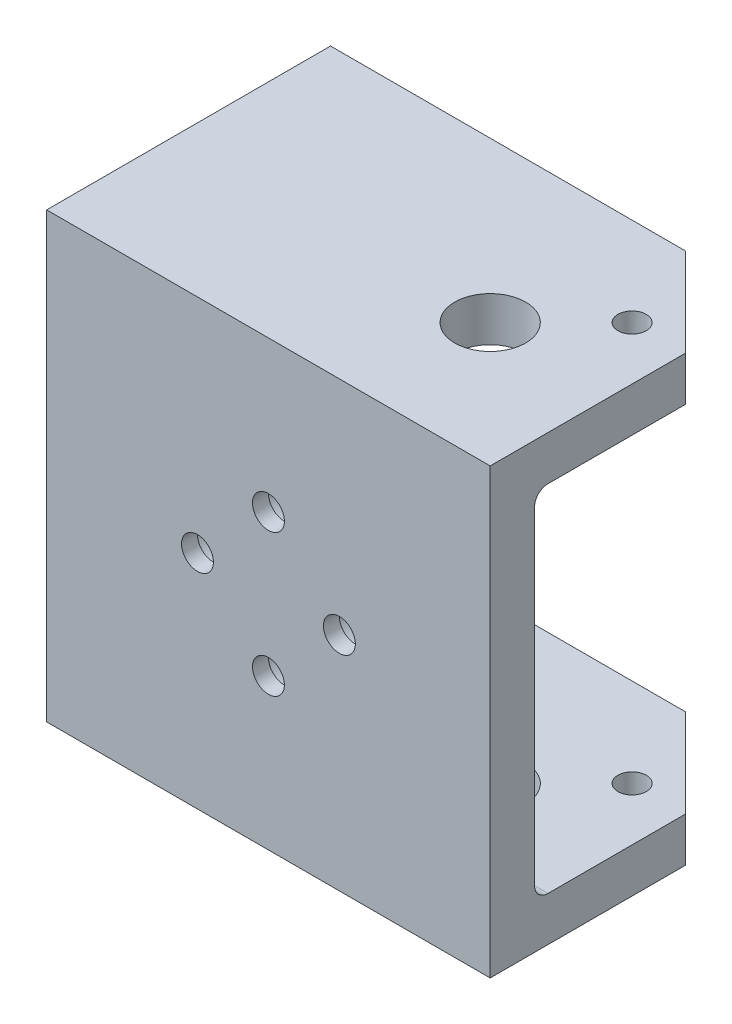
SolidWorks part; units mm, degrees
ref_plane "Front Plane" through (0, 0, 0) normal (0, 0, 1) x (1, 0, 0)
ref_plane "Top Plane" through (0, 0, 0) normal (0, 1, 0) x (1, 0, 0)
ref_plane "Right Plane" through (0, 0, 0) normal (1, 0, 0) x (0, 0, -1)
sketch "Sketch1" plane through (0, 0, 0) normal (0, 0, 1) x (1, 0, 0)
  line L1 (-12.5, 12.5) -> (12.5, 12.5)
  line L2 (-12.5, 12.5) -> (-12.5, -12.5)
  line L3 (-12.5, -12.5) -> (12.5, -12.5)
  line L4 (12.5, 12.5) -> (12.5, -12.5)
  line L5 (-12.5, 12.5) -> (12.5, -12.5) construction
  line L6 (-12.5, -12.5) -> (12.5, 12.5) construction
  point P0 (0, 0)
  dimension "D1" = 25
  dimension "D2" = 25
extrude "Boss-Extrude1" add sketch "Sketch1" along normal blind 2.5
sketch "Sketch2" plane through (0, 0, 0) normal (0, 0, -1) x (-1, 0, 0)
  line L0 (-12.5, -12.5) -> (-12.5, 12.5) construction
  line L1 (12.5, 12.5) -> (-12.5, 12.5)
  line L2 (12.5, 12.5) -> (12.5, 10)
  line L3 (12.5, 10) -> (-12.5, 10)
  line L4 (-12.5, 12.5) -> (-12.5, 10)
  line L5 (12.5, 0) -> (-12.5, 0) construction
  line L6 (12.5, 12.5) -> (12.5, -12.5) construction
  line L7 (12.5, -10) -> (-12.5, -10)
  line L8 (-12.5, -12.5) -> (-12.5, -10)
  line L9 (12.5, -12.5) -> (-12.5, -12.5)
  line L10 (12.5, -12.5) -> (12.5, -10)
  dimension "D1" = 2.5
extrude "Boss-Extrude2" add sketch "Sketch2" along normal blind 13.5
sketch "Sketch10" plane through (0, -12.5, 0) normal (0, -1, 0) x (1, 0, 0)
  line L0 (12.5, 2.5) -> (12.5, -13.5) construction
  line L2 (-12.5, 2.5) -> (12.5, 2.5) construction
  line L3 (12.5, -13.5) -> (-12.5, -13.5) construction
  line L4 (12.5, 2.5) -> (12.5, -13.5) construction
  circle A0 centre (5.5, -4.5) radius 2
  circle A1 centre (9.5, -8.5) radius 0.8
  dimension "D1" = 1.6
  dimension "D2" = 4
  dimension "D3" = 7
  dimension "D4" = 7
  dimension "D5" = 5
  dimension "D6" = 3
extrude "Cut-Extrude1" cut sketch "Sketch10" against normal through all contours A0 region at (5.5, -12.5, -4.5)
extrude "Cut-Extrude2" cut sketch "Sketch10<3>" against normal through all contours A1 region at (9.5, -12.5, -8.5)
sketch "Sketch10<3>" plane through (0, -12.5, 0) normal (0, -1, 0) x (1, 0, 0) same geometry as "Sketch10"
fillet "Fillet1" radius 0.762 2 edges at (0, -10, 0) (0, 10, 0)
chamfer "Chamfer1" distance 5 angle 45 2 edges at (12.5, -11.25, -13.5) (12.5, 11.25, -13.5)
sketch "Sketch12" plane through (0, 0, 0) normal (0, 0, -1) x (-1, 0, 0)
  line L0 (-13.6435, 0) -> (16.7073, 0) construction
hole_wizard "CBORE for M1.6 SHCS1" positions "Sketch13" profile "Sketch14" counterbore size "M1.6" standard "ANSI Metric" end condition through all
sketch "Sketch13" plane through (0, 0, 0) normal (0, 0, -1) x (-1, 0, 0)
  line L0 (-13.6435, 0) -> (16.7073, 0) construction
  line L2 (-13.3169, 0) -> (20.491, 0) construction
  line L3 (-12.5, -9.238) -> (-12.5, 9.238) construction
  point P0 (0, 4)
  point P14 (0, -4)
  point P15 (4, 0)
  point P17 (-4, 0)
  point P21 (0, 4)
  dimension "D1" = 4
  dimension "D2" = 12.5
  dimension "D3" = 4
  dimension "D4" = 4
sketch "Sketch14" plane through (0, 4, 0) normal (1, 0, 0) x (0, 1, 0)
  line L0 (0, 0) -> (0, 2.5)
  line L1 (0, 2.5) -> (0.9, 2.5)
  line L3 (0.9, 2.5) -> (0.9, 1.6)
  line L4 (1.75, 1.6) -> (0.9, 1.6)
  line L5 (1.75, 1.6) -> (1.75, 0.025)
  line L6 (1.75, 0.025) -> (1.775, 0)
  line L7 (1.775, 0) -> (0, 0)
  line L8 (-1.75, 0.025) -> (-1.775, 0) construction
  line L11 (0, -6.35) -> (0, 107.95) construction
  dimension "Thru Hole Dia." = 1.8
  dimension "Thru Hole Depth" = 2.5
  dimension "C'Bore Dia." = 3.5
  dimension "C'Bore Depth" = 1.6
  dimension "Near C'Sink Dia." = 3.55
  dimension "Near C'Sink Angle" = 90
